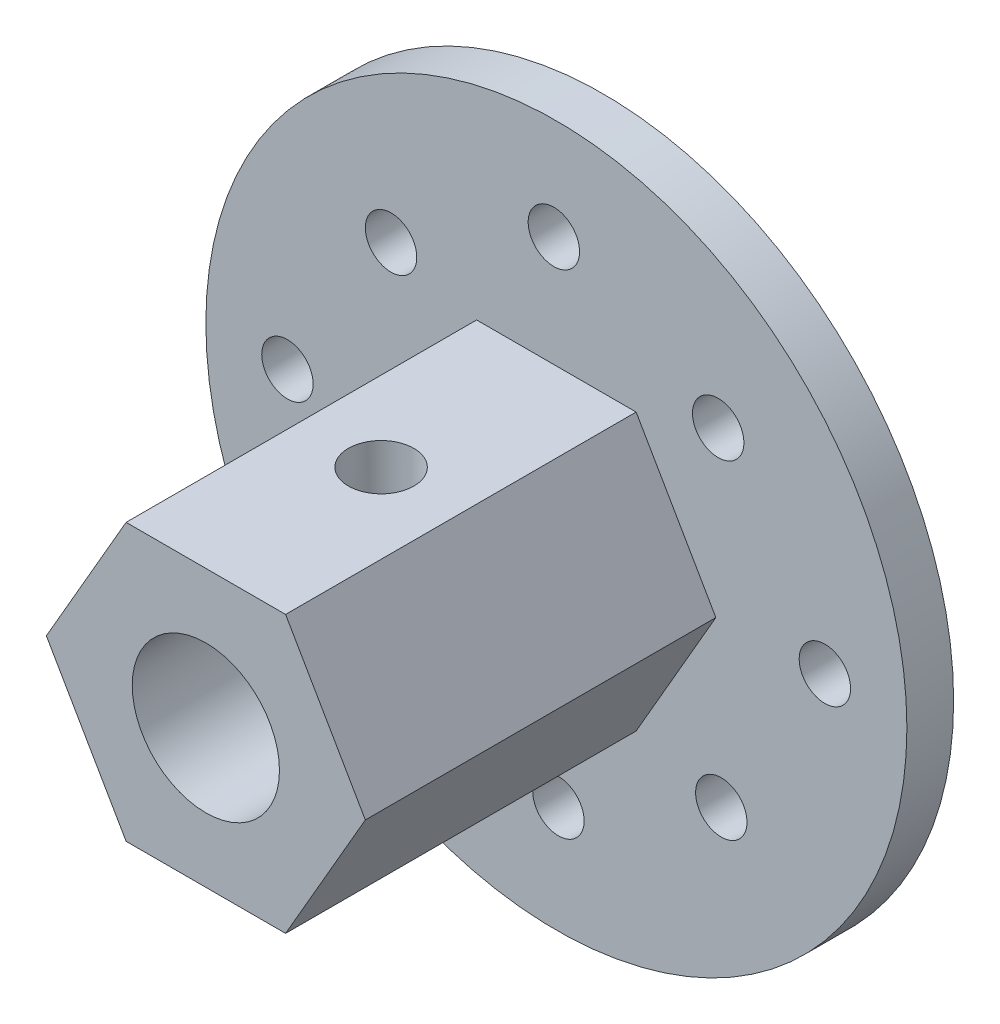
SolidWorks part; units mm, degrees
ref_plane "前视基准面" through (0, 0, 0) normal (0, 0, 1) x (1, 0, 0)
ref_plane "上视基准面" through (0, 0, 0) normal (0, 1, 0) x (1, 0, 0)
ref_plane "右视基准面" through (0, 0, 0) normal (1, 0, 0) x (0, 0, -1)
other "Configuration Table"
sketch "草图1" plane through (0, 0, 0) normal (0, 0, 1) x (1, 0, 0)
  line L1 (6.825, 0) -> (3.4125, 5.9106)
  line L2 (3.4125, 5.9106) -> (-3.4125, 5.9106)
  line L3 (-3.4125, 5.9106) -> (-6.825, 0)
  line L4 (-6.825, 0) -> (-3.4125, -5.9106)
  line L5 (-3.4125, -5.9106) -> (3.4125, -5.9106)
  line L6 (3.4125, -5.9106) -> (6.825, 0)
  circle A1 centre (0, 0) radius 6.825 construction
  circle A2 centre (0, 0) radius 3.15
  dimension "D1" = 6.3
extrude "凸台-拉伸1" add sketch "草图1" along normal blind 15 contours L5 L6 L1 L2 L3 L4 A2 region at (4.9624, -2.865, 0)
sketch "草图2" plane through (0, 0, 0) normal (0, 0, -1) x (-1, 0, 0)
  circle A0 centre (0, 0) radius 15
  circle A1 centre (0, 0) radius 3.15
  circle A2 centre (0.1078, 10.6418) radius 1.1
  circle A3 centre (7.0747, 6.9494) radius 1.1
  circle A4 centre (11.5093, 0.0349) radius 1.1
  circle A5 centre (6.9424, -7.0504) radius 1.1
  circle A6 centre (-0.088, -10.3573) radius 1.1
  circle A7 centre (-7.0576, -6.9195) radius 1.1
  circle A8 centre (-11.4897, 0.2494) radius 1.1
  circle A9 centre (-6.9245, 7.0773) radius 1.1
  dimension "D1" = 2.2
  dimension "D2" = 2.2
  dimension "D3" = 2.2
  dimension "D4" = 2.2
  dimension "D5" = 2.2
  dimension "D6" = 2.2
  dimension "D7" = 2.2
  dimension "D8" = 2.2
  dimension "D9" = 6.3
extrude "凸台-拉伸2" add sketch "草图2" along normal blind 2
sketch "草图3" plane through (0, 5.9106, 0) normal (0, 1, 0) x (1, 0, 0)
  line L0 (3.4125, -7.5) -> (-3.4125, -7.5) construction
  line L1 (3.4125, -15) -> (3.4125, 0) construction
  line L2 (-3.4125, -15) -> (-3.4125, 0) construction
  circle A0 centre (0, -7.5) radius 1.4
extrude "切除-拉伸1" cut sketch "草图3" against normal through all
